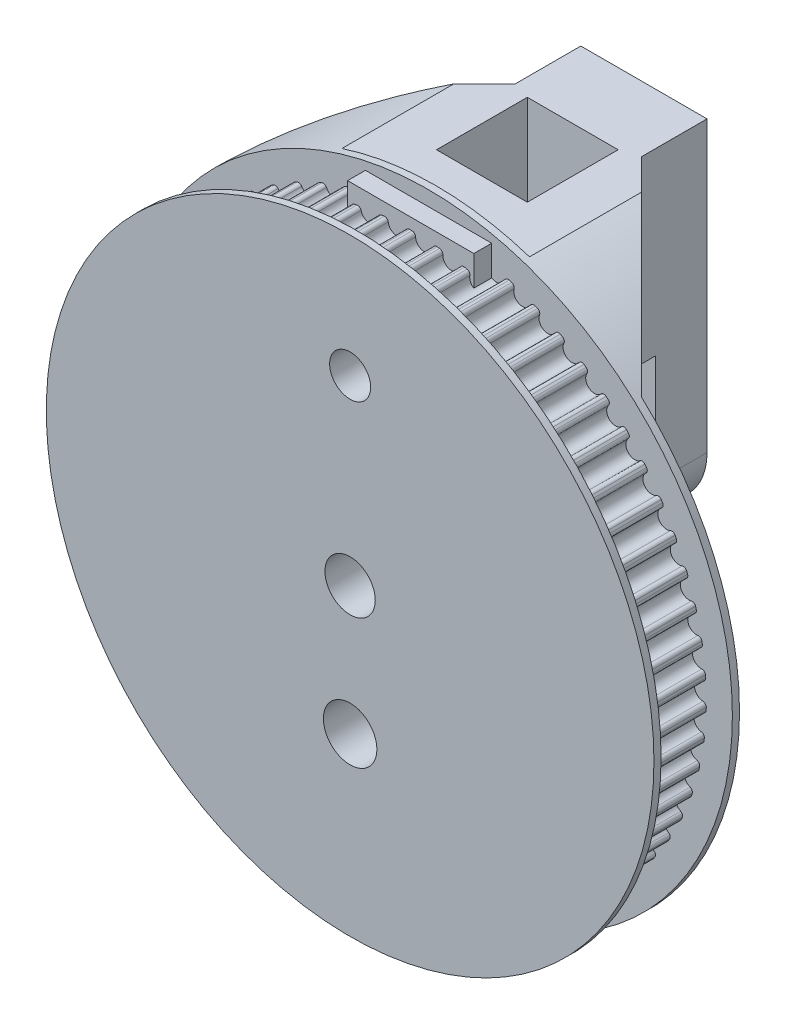
SolidWorks part; units mm, degrees
other "Markup1"
sketch "Sketch12" plane through (-30, -58, 49.7) normal (-0.8709, -0.4905, 0.0319) x (-0.1533, 0.2093, -0.9658)
other "Markup2"
sketch "Sketch14" plane through (30, -60, 49.7) normal (0.6168, -0.7172, 0.3243) x (-0.4689, -0.0038, 0.8832)
material "PETG"
ref_plane "Front Plane" through (0, 0, 0) normal (0, 0, 1) x (1, 0, 0)
ref_plane "Top Plane" through (0, 0, 0) normal (0, 1, 0) x (1, 0, 0)
ref_plane "Right Plane" through (0, 0, 0) normal (1, 0, 0) x (0, 0, -1)
sketch "Sketch1" plane through (0, 0, 0) normal (0, 1, 0) x (1, 0, 0)
  line L1 (-12.7375, -12.7375) -> (12.7375, -12.7375)
  line L2 (-12.7375, -12.7375) -> (-12.7375, 12.7375)
  line L3 (-12.7375, 12.7375) -> (12.7375, 12.7375)
  line L4 (12.7375, -12.7375) -> (12.7375, 12.7375)
  line L5 (-17.7, -17.7) -> (17.7, -17.7)
  line L6 (-17.7, -17.7) -> (-17.7, 17.7)
  line L7 (-17.7, 17.7) -> (17.7, 17.7)
  line L8 (17.7, -17.7) -> (17.7, 17.7)
  point P8 (0, -17.7)
  point P9 (0, -12.7375)
  point P12 (-17.7, 0)
  point P13 (-12.7375, 0)
  dimension "D1" = 25.475
  dimension "D2" = 35.4
extrude "Boss-Extrude1" add sketch "Sketch1" along normal blind 47.0375
extrude "Boss-Extrude2" add sketch "Sketch1<3>" against normal blind 14.9625 contours L1 L4 L3 L2 | L5 L8 L7 L6 L4 L1 L2 L3 region at (0, 0, 0) region at (-17.1994, 0, 0)
sketch "Sketch1<3>" plane through (0, 0, 0) normal (0, 1, 0) x (1, 0, 0) same geometry as "Sketch1"
sketch "Sketch3" plane through (0, 0, 0) normal (0, -1, 0) x (-1, 0, 0)
  circle A0 centre (0, 0) radius 3.15
  dimension "D1" = 6.3
extrude "Cut-Extrude1" cut sketch "Sketch3" along normal through all
sketch "Sketch13" plane through (0, -14.9625, 0) normal (0, -1, 0) x (1, 0, 0)
  circle A0 centre (0, 0) radius 5.5
  dimension "D1" = 11
extrude "Cut-Extrude4" cut sketch "Sketch13" against normal offset from surface (6.9625 mm away) 8 up to face at (0, 0, -3.15)
sketch "Sketch4" plane through (0, 0, 17.7) normal (0, 0, 1) x (1, 0, 0)
  line L0 (17.7, 47.0375) -> (17.7, -14.9625) construction
  line L1 (-17.7, 47.0375) -> (-17.7, -14.9625) construction
  line L2 (17.7, -34.0125) -> (17.7, -14.9625)
  line L3 (-17.7, -34.0125) -> (-17.7, -14.9625)
  line L5 (17.7, 47.0375) -> (-17.7, 47.0375)
  line L6 (17.7, 47.0375) -> (17.7, -14.9625)
  line L8 (-17.7, 47.0375) -> (-17.7, -14.9625)
  line L9 (-17.7, -14.9625) -> (17.7, -14.9625) construction
  line L10 (-17.7, 47.0375) -> (17.7, 47.0375) construction
  arc A0 (-17.7, -34.0125) -> (17.7, -34.0125) centre (0, -34.0125) ccw
  circle A1 centre (0, -34.0125) radius 7.05
  dimension "D2" = 14.1
  dimension "D1" = 19.05
extrude "Boss-Extrude3" add sketch "Sketch4" along normal blind 15
sketch "Sketch6" plane through (0, 0, 17.7) normal (0, 0, -1) x (-1, 0, 0)
  line L0 (17.7, -34.0125) -> (17.7, -14.9625)
  line L1 (17.7, -14.9625) -> (-17.7, -14.9625)
  line L2 (-17.7, -14.9625) -> (-17.7, -34.0125)
  arc A0 (-17.7, -34.0125) -> (17.7, -34.0125) centre (0, -34.0125) ccw
  arc A4 (-17.7, -34.0125) -> (17.7, -34.0125) centre (0, -34.0125) ccw construction
extrude "Cut-Extrude2" cut sketch "Sketch6" against normal blind 0.5375
sketch "Sketch7" plane through (0, 0, 18.2375) normal (0, 0, -1) x (-1, 0, 0)
  circle A0 centre (0, -34.0125) radius 11.0375
  arc A1 (-17.7, -34.0125) -> (17.7, -34.0125) centre (0, -34.0125) ccw construction
  dimension "D1" = 22.075
extrude "Cut-Extrude3" cut sketch "Sketch7" against normal blind 7
mirror "Mirror1" about plane through (0, 0, 0) normal (0, 0, 1) of "Boss-Extrude3", "Cut-Extrude2", "Cut-Extrude1", "Cut-Extrude3"
sketch "Sketch18" plane through (0, 0, 0) normal (0, 0, 1) x (1, 0, 0)
  line L0 (0, -13.5166) -> (-17.7, -3.2975)
  line L1 (-17.7, -3.2975) -> (-35.45, -34.0414) construction
  line L2 (-35.45, -34.0414) -> (-8.875, -49.3845) construction
  line L3 (-17.7, 47.0375) -> (-17.7, -34.0125) construction
  line L4 (0, -35.0322) -> (0, -50035.0322) construction
  line L5 (-17.7, -3.2975) -> (-17.7, -14.9625)
  line L6 (17.7, -34.0125) -> (17.7, 47.0375) construction
  line L7 (17.7, -3.2975) -> (0, -13.5166)
  line L10 (17.7, -14.9625) -> (17.7, -3.2975)
  line L11 (-17.7, -14.9625) -> (17.7, -14.9625)
  line L12 (-5.5, -14.9625) -> (5.5, -14.9625) construction
  circle A0 centre (0, -34.0125) radius 17.75 construction
  arc A2 (-17.7, -34.0125) -> (17.7, -34.0125) centre (0, -34.0125) ccw construction
  dimension "D2" = 120
  dimension "D1" = 35.5
extrude "Cut-Extrude10" cut sketch "Sketch18" along normal up to surface and the other way up to surface up to face at (-11.0375, -34.0125, 18.2375) other way up to face at (-11.0375, -34.0125, -18.2375)
ref_plane "Plane1" through (0, 0, 27.7) normal (0, 0, 1) x (1, 0, 0)
sketch "Sketch9" plane through (0, 0, 27.7) normal (0, 0, 1) x (1, 0, 0)
  circle A0 centre (0, -34.0125) radius 85.2141
  circle A1 centre (0, -34.0125) radius 7.05 construction
  circle A2 centre (0, -34.0125) radius 7.05
  dimension "D1" = 170.4282
extrude "Boss-Extrude4" add sketch "Sketch9" against normal blind 2 contours A0 region at (-82.8039, -34.0125, 27.7)
sketch "Sketch10" plane through (0, 0, 27.7) normal (0, 0, -1) x (-1, 0, 0)
  line L0 (0, -41.0625) -> (0, -50041.0625) construction
  line L1 (0, -34.0125) -> (-3.9983, -114.1269) construction
  line L2 (0, -34.0125) -> (3.9983, -114.1269) construction
  circle A0 centre (0, -34.0125) radius 80.2141 construction
  circle A1 centre (0, -34.0125) radius 7.05
  circle A2 centre (0, -34.0125) radius 85.2141 construction
  circle A3 centre (0, -34.0125) radius 7.05 construction
  arc A4 (2.4815, -110.9206) -> (-2.4815, -110.9206) centre (0, -111.1266) ccw
  arc A5 (-3.5233, -111.8369) -> (-2.4815, -110.9206) centre (-3.478, -110.8379) ccw
  circle A6 centre (0, -34.0125) radius 77.9041 construction
  arc A7 (2.4815, -110.9206) -> (3.5233, -111.8369) centre (3.478, -110.8379) ccw
  arc A8 (3.5233, -111.8369) -> (3.8832, -111.8198) centre (0, -34.0125) ccw
  arc A9 (-3.8832, -111.8198) -> (-3.5233, -111.8369) centre (0, -34.0125) ccw
  arc A10 (-11.611, -111.0465) -> (-11.2546, -111.0993) centre (0, -34.0125) ccw
  arc A11 (-11.2546, -111.0993) -> (-10.1267, -110.2914) centre (-11.1101, -110.1098) ccw
  arc A12 (-5.1884, -110.7855) -> (-10.1267, -110.2914) centre (-7.6781, -110.7434) ccw
  arc A13 (-5.1884, -110.7855) -> (-4.243, -111.801) centre (-4.1886, -110.8024) ccw
  arc A14 (-4.243, -111.801) -> (-3.8832, -111.8198) centre (0, -34.0125) ccw
  arc A15 (-19.2234, -109.5076) -> (-18.874, -109.5957) centre (0, -34.0125) ccw
  arc A16 (-18.874, -109.5957) -> (-17.6713, -108.904) centre (-18.6317, -108.6255) ccw
  arc A17 (-12.8068, -109.8874) -> (-17.6713, -108.904) centre (-15.2799, -109.5976) ccw
  arc A18 (-12.8068, -109.8874) -> (-11.9672, -110.9919) centre (-11.8136, -110.0038) ccw
  arc A19 (-11.9672, -110.9919) -> (-11.611, -111.0465) centre (0, -34.0125) ccw
  arc A20 (-26.6448, -107.2184) -> (-26.3059, -107.3409) centre (0, -34.0125) ccw
  arc A21 (-26.3059, -107.3409) -> (-25.0403, -106.7724) centre (-25.9682, -106.3996) ccw
  arc A22 (-20.2978, -108.2352) -> (-25.0403, -106.7724) centre (-22.7298, -107.7006) ccw
  arc A23 (-20.2978, -108.2352) -> (-19.5724, -109.4179) centre (-19.3212, -108.4499) ccw
  arc A24 (-19.5724, -109.4179) -> (-19.2234, -109.5076) centre (0, -34.0125) ccw
  arc A25 (-33.8013, -104.2017) -> (-33.4763, -104.3573) centre (0, -34.0125) ccw
  arc A26 (-33.4763, -104.3573) -> (-32.1604, -103.9176) centre (-33.0466, -103.4543) ccw
  arc A27 (-27.5872, -105.8454) -> (-32.1604, -103.9176) centre (-29.9538, -105.0713) ccw
  arc A28 (-27.5872, -105.8454) -> (-26.9831, -107.0944) centre (-26.6367, -106.1563) ccw
  arc A29 (-26.9831, -107.0944) -> (-26.6448, -107.2184) centre (0, -34.0125) ccw
  arc A30 (-40.6219, -100.4874) -> (-40.314, -100.6745) centre (0, -34.0125) ccw
  arc A31 (-40.314, -100.6745) -> (-38.9609, -100.3681) centre (-39.7965, -99.8188) ccw
  arc A32 (-34.6023, -102.7416) -> (-38.9609, -100.3681) centre (-36.8801, -101.7358) ccw
  arc A33 (-34.6023, -102.7416) -> (-34.1256, -104.0446) centre (-33.6876, -103.1456) ccw
  arc A34 (-34.1256, -104.0446) -> (-33.8013, -104.2017) centre (0, -34.0125) ccw
  arc A35 (-47.0388, -96.1124) -> (-46.7511, -96.3293) centre (0, -34.0125) ccw
  arc A36 (-46.7511, -96.3293) -> (-45.3742, -96.1591) centre (-46.151, -95.5294) ccw
  arc A37 (-41.2736, -98.9548) -> (-45.3742, -96.1591) centre (-43.4399, -97.7272) ccw
  arc A38 (-41.2736, -98.9548) -> (-40.929, -100.2987) centre (-40.4036, -99.4479) ccw
  arc A39 (-40.929, -100.2987) -> (-40.6219, -100.4874) centre (0, -34.0125) ccw
  arc A40 (-52.9882, -91.1202) -> (-52.7235, -91.3647) centre (0, -34.0125) ccw
  arc A41 (-52.7235, -91.3647) -> (-51.3365, -91.3325) centre (-52.0467, -90.6285) ccw
  arc A42 (-47.5347, -94.5226) -> (-51.3365, -91.3325) centre (-49.568, -93.0853) ccw
  arc A43 (-47.5347, -94.5226) -> (-47.3256, -95.8941) centre (-46.7181, -95.0998) ccw
  arc A44 (-47.3256, -95.8941) -> (-47.0388, -96.1124) centre (0, -34.0125) ccw
  arc A45 (-58.411, -85.5605) -> (-58.172, -85.8302) centre (0, -34.0125) ccw
  arc A46 (-58.172, -85.8302) -> (-56.7886, -85.9362) centre (-57.4253, -85.165) ccw
  arc A47 (-53.3233, -89.489) -> (-56.7886, -85.9362) centre (-55.2034, -87.8564) ccw
  arc A48 (-53.3233, -89.489) -> (-53.2518, -90.8745) centre (-52.5683, -90.1446) ccw
  arc A49 (-53.2518, -90.8745) -> (-52.9882, -91.1202) centre (0, -34.0125) ccw
  arc A50 (-63.2533, -79.4885) -> (-63.0423, -79.7806) centre (0, -34.0125) ccw
  arc A51 (-63.0423, -79.7806) -> (-61.6764, -80.0238) centre (-62.233, -79.1931) ccw
  arc A52 (-58.582, -83.904) -> (-61.6764, -80.0238) centre (-60.2902, -82.0923) ccw
  arc A53 (-58.582, -83.904) -> (-58.6488, -85.2898) centre (-57.896, -84.6316) ccw
  arc A54 (-58.6488, -85.2898) -> (-58.411, -85.5605) centre (0, -34.0125) ccw
  arc A55 (-67.4669, -72.9645) -> (-67.286, -73.2762) centre (0, -34.0125) ccw
  arc A56 (-67.286, -73.2762) -> (-65.9511, -73.6542) centre (-66.4223, -72.7722) ccw
  arc A57 (-63.2585, -77.8232) -> (-65.9511, -73.6542) centre (-64.7778, -75.8505) ccw
  arc A58 (-63.2585, -77.8232) -> (-63.463, -79.1955) centre (-62.6483, -78.6155) ccw
  arc A59 (-63.463, -79.1955) -> (-63.2533, -79.4885) centre (0, -34.0125) ccw
  arc A60 (-71.01, -66.0534) -> (-70.8611, -66.3816) centre (0, -34.0125) ccw
  arc A61 (-70.8611, -66.3816) -> (-69.5704, -66.8906) centre (-69.9515, -65.9661) ccw
  arc A62 (-67.3063, -71.307) -> (-69.5704, -66.8906) centre (-68.6217, -69.1928) ccw
  arc A63 (-67.3063, -71.307) -> (-67.6464, -72.6521) centre (-66.778, -72.1561) ccw
  arc A64 (-67.6464, -72.6521) -> (-67.4669, -72.9645) centre (0, -34.0125) ccw
  arc A65 (-73.8474, -58.8239) -> (-73.7319, -59.1652) centre (0, -34.0125) ccw
  arc A66 (-73.7319, -59.1652) -> (-72.4983, -59.8003) centre (-72.7854, -58.8424) ccw
  arc A67 (-70.6852, -64.4201) -> (-72.4983, -59.8003) centre (-71.7835, -62.1854) ccw
  arc A68 (-70.6852, -64.4201) -> (-71.1575, -65.7247) centre (-70.2441, -65.3176) ccw
  arc A69 (-71.1575, -65.7247) -> (-71.01, -66.0534) centre (0, -34.0125) ccw
  arc A70 (-75.9509, -51.3478) -> (-75.8699, -51.6989) centre (0, -34.0125) ccw
  arc A71 (-75.8699, -51.6989) -> (-74.7057, -52.4536) centre (-74.896, -51.4719) ccw
  arc A72 (-73.3615, -57.2311) -> (-74.7057, -52.4536) centre (-74.2319, -54.8981) ccw
  arc A73 (-73.3615, -57.2311) -> (-73.9614, -58.4821) centre (-73.012, -58.168) ccw
  arc A74 (-73.9614, -58.4821) -> (-73.8474, -58.8239) centre (0, -34.0125) ccw
  arc A75 (-77.2995, -43.6994) -> (-77.2539, -44.0568) centre (0, -34.0125) ccw
  arc A76 (-77.2539, -44.0568) -> (-76.1706, -44.9237) centre (-76.2622, -43.9279) ccw
  arc A77 (-75.3088, -49.8112) -> (-76.1706, -44.9237) centre (-75.9426, -47.4032) ccw
  arc A78 (-75.3088, -49.8112) -> (-76.0302, -50.9963) centre (-75.0543, -50.7783) ccw
  arc A79 (-76.0302, -50.9963) -> (-75.9509, -51.3478) centre (0, -34.0125) ccw
  arc A80 (-77.8799, -35.9547) -> (-77.8701, -36.3149) centre (0, -34.0125) ccw
  arc A81 (-77.8701, -36.3149) -> (-76.8785, -37.2853) centre (-76.8705, -36.2854) ccw
  arc A82 (-76.5076, -42.2344) -> (-76.8785, -37.2853) centre (-76.8985, -39.7752) ccw
  arc A83 (-76.5076, -42.2344) -> (-77.3435, -43.3417) centre (-76.3507, -43.222) ccw
  arc A84 (-77.3435, -43.3417) -> (-77.2995, -43.6994) centre (0, -34.0125) ccw
  arc A85 (-77.6863, -28.1907) -> (-77.7124, -28.5501) centre (0, -34.0125) ccw
  arc A86 (-77.7124, -28.5501) -> (-76.8224, -29.6144) centre (-76.7148, -28.6202) ccw
  arc A87 (-76.9461, -34.5758) -> (-76.8224, -29.6144) centre (-77.0901, -32.09) ccw
  arc A88 (-76.9461, -34.5758) -> (-77.888, -35.5945) centre (-76.8882, -35.5741) ccw
  arc A89 (-77.888, -35.5945) -> (-77.8799, -35.9547) centre (0, -34.0125) ccw
  arc A90 (-76.7206, -20.4846) -> (-76.7823, -20.8396) centre (0, -34.0125) ccw
  arc A91 (-76.7823, -20.8396) -> (-76.0027, -21.9873) centre (-75.7967, -21.0087) ccw
  arc A92 (-76.6198, -26.9117) -> (-76.0027, -21.9873) centre (-76.5156, -24.4238) ccw
  arc A93 (-76.6198, -26.9117) -> (-77.6585, -27.8315) centre (-76.6616, -27.9108) ccw
  arc A94 (-77.6585, -27.8315) -> (-77.6863, -28.1907) centre (0, -34.0125) ccw
  arc A95 (-74.9924, -12.9129) -> (-75.0892, -13.26) centre (0, -34.0125) ccw
  arc A96 (-75.0892, -13.26) -> (-74.4277, -14.4796) centre (-74.1253, -13.5264) ccw
  arc A97 (-75.5321, -19.3181) -> (-74.4277, -14.4796) centre (-75.1807, -16.853) ccw
  arc A98 (-75.5321, -19.3181) -> (-76.6572, -20.1299) centre (-75.6732, -20.3081) ccw
  arc A99 (-76.6572, -20.1299) -> (-76.7206, -20.4846) centre (0, -34.0125) ccw
  arc A100 (-72.5189, -5.5509) -> (-72.6497, -5.8867) centre (0, -34.0125) ccw
  arc A101 (-72.6497, -5.8867) -> (-72.113, -7.166) centre (-71.7172, -6.2477) ccw
  arc A102 (-73.6936, -11.8705) -> (-72.113, -7.166) centre (-73.0986, -9.4527) ccw
  arc A103 (-73.6936, -11.8705) -> (-74.894, -12.5663) centre (-73.9326, -12.8416) ccw
  arc A104 (-74.894, -12.5663) -> (-74.9924, -12.9129) centre (0, -34.0125) ccw
  arc A105 (-69.3247, 1.5282) -> (-69.4883, 1.2071) centre (0, -34.0125) ccw
  arc A106 (-69.4883, 1.2071) -> (-69.0816, -0.1193) centre (-68.5963, 0.7551) ccw
  arc A107 (-71.1228, -4.6431) -> (-69.0816, -0.1193) centre (-70.2899, -2.2965) ccw
  arc A108 (-71.1228, -4.6431) -> (-72.3865, -5.2158) centre (-71.4573, -5.5855) ccw
  arc A109 (-72.3865, -5.2158) -> (-72.5189, -5.5509) centre (0, -34.0125) ccw
  arc A110 (-65.4415, 8.2541) -> (-65.6363, 7.9509) centre (0, -34.0125) ccw
  arc A111 (-65.6363, 7.9509) -> (-65.3637, 6.5906) centre (-64.7937, 7.4123) ccw
  arc A112 (-67.8451, 2.2925) -> (-65.3637, 6.5906) centre (-66.7828, 4.5445) ccw
  arc A113 (-67.8451, 2.2925) -> (-69.1595, 1.8485) centre (-68.2718, 1.3881) ccw
  arc A114 (-69.1595, 1.8485) -> (-69.3247, 1.5282) centre (0, -34.0125) ccw
  arc A115 (-60.9079, 14.5599) -> (-61.1319, 14.2777) centre (0, -34.0125) ccw
  arc A116 (-61.1319, 14.2777) -> (-60.9961, 12.8969) centre (-60.3472, 13.6578) ccw
  arc A117 (-63.8932, 8.8673) -> (-60.9961, 12.8969) centre (-62.6119, 11.0024) ccw
  arc A118 (-63.8932, 8.8673) -> (-65.2453, 8.5563) centre (-64.4077, 8.0099) ccw
  arc A119 (-65.2453, 8.5563) -> (-65.4415, 8.2541) centre (0, -34.0125) ccw
  arc A120 (-55.769, 20.383) -> (-56.02, 20.1245) centre (0, -34.0125) ccw
  arc A121 (-56.02, 20.1245) -> (-56.0223, 18.7371) centre (-55.3009, 19.4295) ccw
  arc A122 (-59.3062, 15.016) -> (-56.0223, 18.7371) centre (-57.8187, 17.0128) ccw
  arc A123 (-59.3062, 15.016) -> (-60.6826, 14.8411) centre (-59.9036, 14.214) ccw
  arc A124 (-60.6826, 14.8411) -> (-60.9079, 14.5599) centre (0, -34.0125) ccw
  arc A125 (-50.0758, 25.6655) -> (-50.3513, 25.4332) centre (0, -34.0125) ccw
  arc A126 (-50.3513, 25.4332) -> (-50.4918, 24.053) centre (-49.705, 24.6702) ccw
  arc A127 (-54.1299, 20.6773) -> (-50.4918, 24.053) centre (-52.4509, 22.5161) ccw
  arc A128 (-54.1299, 20.6773) -> (-55.5168, 20.6404) centre (-54.8041, 19.9388) ccw
  arc A129 (-55.5168, 20.6404) -> (-55.769, 20.383) centre (0, -34.0125) ccw
  arc A130 (-43.8849, 30.3549) -> (-44.1822, 30.1512) centre (0, -34.0125) ccw
  arc A131 (-44.1822, 30.1512) -> (-44.4594, 28.7918) centre (-43.6151, 29.3276) ccw
  arc A132 (-48.4155, 25.7951) -> (-44.4594, 28.7918) centre (-46.5618, 27.4576) ccw
  arc A133 (-48.4155, 25.7951) -> (-49.7992, 25.8965) centre (-49.16, 25.1275) ccw
  arc A134 (-49.7992, 25.8965) -> (-50.0758, 25.6655) centre (0, -34.0125) ccw
  arc A135 (-37.2579, 34.4046) -> (-37.574, 34.2315) centre (0, -34.0125) ccw
  arc A136 (-37.574, 34.2315) -> (-37.9852, 32.9064) centre (-37.0917, 33.3555) ccw
  arc A137 (-42.22, 30.3186) -> (-37.9852, 32.9064) centre (-40.21, 31.7883) ccw
  arc A138 (-42.22, 30.3186) -> (-43.5867, 30.5572) centre (-43.0272, 29.7283) ccw
  arc A139 (-43.5867, 30.5572) -> (-43.8849, 30.3549) centre (0, -34.0125) ccw
  arc A140 (-30.2607, 37.7743) -> (-30.5924, 37.6335) centre (0, -34.0125) ccw
  arc A141 (-30.5924, 37.6335) -> (-31.1335, 36.356) centre (-30.1997, 36.7139) ccw
  arc A142 (-35.6049, 34.2027) -> (-31.1335, 36.356) centre (-33.4586, 35.4649) ccw
  arc A143 (-35.6049, 34.2027) -> (-36.9411, 34.5762) centre (-36.4669, 33.6957) ccw
  arc A144 (-36.9411, 34.5762) -> (-37.2579, 34.4046) centre (0, -34.0125) ccw
  arc A145 (-22.9626, 40.4305) -> (-23.3067, 40.3235) centre (0, -34.0125) ccw
  arc A146 (-23.3067, 40.3235) -> (-23.9723, 39.1062) centre (-23.0075, 39.3693) ccw
  arc A147 (-28.6359, 37.4088) -> (-23.9723, 39.1062) centre (-26.3746, 38.451) ccw
  arc A148 (-28.6359, 37.4088) -> (-29.9283, 37.9135) centre (-29.5441, 36.9902) ccw
  arc A149 (-29.9283, 37.9135) -> (-30.2607, 37.7743) centre (0, -34.0125) ccw
  arc A150 (-15.4364, 42.3469) -> (-15.7894, 42.2747) centre (0, -34.0125) ccw
  arc A151 (-15.7894, 42.2747) -> (-16.5729, 41.1297) centre (-15.5867, 41.2955) ccw
  arc A152 (-21.3824, 39.9051) -> (-16.5729, 41.1297) centre (-19.0285, 40.717) ccw
  arc A153 (-21.3824, 39.9051) -> (-22.6181, 40.5359) centre (-22.3277, 39.579) ccw
  arc A154 (-22.6181, 40.5359) -> (-22.9626, 40.4305) centre (0, -34.0125) ccw
  arc A155 (-7.7567, 43.5045) -> (-8.1152, 43.4678) centre (0, -34.0125) ccw
  arc A156 (-8.1152, 43.4678) -> (-9.0088, 42.4065) centre (-8.011, 42.4732) ccw
  arc A157 (-13.9163, 41.6668) -> (-9.0088, 42.4065) centre (-11.4933, 42.2403) ccw
  arc A158 (-13.9163, 41.6668) -> (-15.083, 42.4175) centre (-14.8894, 41.4365) ccw
  arc A159 (-15.083, 42.4175) -> (-15.4364, 42.3469) centre (0, -34.0125) ccw
  arc A160 (0, 43.8916) -> (-0.3603, 43.8908) centre (0, -34.0125) ccw
  arc A161 (-0.3603, 43.8908) -> (-1.3552, 42.9237) centre (-0.3557, 42.8908) ccw
  arc A162 (-6.3119, 42.6763) -> (-1.3552, 42.9237) centre (-3.8438, 43.0057) ccw
  arc A163 (-6.3119, 42.6763) -> (-7.3981, 43.5395) centre (-7.3031, 42.544) ccw
  arc A164 (-7.3981, 43.5395) -> (-7.7567, 43.5045) centre (0, -34.0125) ccw
  arc A165 (7.7567, 43.5045) -> (7.3981, 43.5395) centre (0, -34.0125) ccw
  arc A166 (7.3981, 43.5395) -> (6.3119, 42.6763) centre (7.3031, 42.544) ccw
  arc A167 (1.3552, 42.9237) -> (6.3119, 42.6763) centre (3.8438, 43.0057) ccw
  arc A168 (1.3552, 42.9237) -> (0.3603, 43.8908) centre (0.3557, 42.8908) ccw
  arc A169 (0.3603, 43.8908) -> (0, 43.8916) centre (0, -34.0125) ccw
  arc A170 (15.4364, 42.3469) -> (15.083, 42.4175) centre (0, -34.0125) ccw
  arc A171 (15.083, 42.4175) -> (13.9163, 41.6668) centre (14.8894, 41.4365) ccw
  arc A172 (9.0088, 42.4065) -> (13.9163, 41.6668) centre (11.4933, 42.2403) ccw
  arc A173 (9.0088, 42.4065) -> (8.1152, 43.4678) centre (8.011, 42.4732) ccw
  arc A174 (8.1152, 43.4678) -> (7.7567, 43.5045) centre (0, -34.0125) ccw
  arc A175 (22.9626, 40.4305) -> (22.6181, 40.5359) centre (0, -34.0125) ccw
  arc A176 (22.6181, 40.5359) -> (21.3824, 39.9051) centre (22.3277, 39.579) ccw
  arc A177 (16.5729, 41.1297) -> (21.3824, 39.9051) centre (19.0285, 40.717) ccw
  arc A178 (16.5729, 41.1297) -> (15.7894, 42.2747) centre (15.5867, 41.2955) ccw
  arc A179 (15.7894, 42.2747) -> (15.4364, 42.3469) centre (0, -34.0125) ccw
  arc A180 (30.2607, 37.7743) -> (29.9283, 37.9135) centre (0, -34.0125) ccw
  arc A181 (29.9283, 37.9135) -> (28.6359, 37.4088) centre (29.5441, 36.9902) ccw
  arc A182 (23.9723, 39.1062) -> (28.6359, 37.4088) centre (26.3746, 38.451) ccw
  arc A183 (23.9723, 39.1062) -> (23.3067, 40.3235) centre (23.0075, 39.3693) ccw
  arc A184 (23.3067, 40.3235) -> (22.9626, 40.4305) centre (0, -34.0125) ccw
  arc A185 (37.2579, 34.4046) -> (36.9411, 34.5762) centre (0, -34.0125) ccw
  arc A186 (36.9411, 34.5762) -> (35.6049, 34.2027) centre (36.4669, 33.6957) ccw
  arc A187 (31.1335, 36.356) -> (35.6049, 34.2027) centre (33.4586, 35.4649) ccw
  arc A188 (31.1335, 36.356) -> (30.5924, 37.6335) centre (30.1997, 36.7139) ccw
  arc A189 (30.5924, 37.6335) -> (30.2607, 37.7743) centre (0, -34.0125) ccw
  arc A190 (43.8849, 30.3549) -> (43.5867, 30.5572) centre (0, -34.0125) ccw
  arc A191 (43.5867, 30.5572) -> (42.22, 30.3186) centre (43.0272, 29.7283) ccw
  arc A192 (37.9852, 32.9064) -> (42.22, 30.3186) centre (40.21, 31.7883) ccw
  arc A193 (37.9852, 32.9064) -> (37.574, 34.2315) centre (37.0917, 33.3555) ccw
  arc A194 (37.574, 34.2315) -> (37.2579, 34.4046) centre (0, -34.0125) ccw
  arc A195 (50.0758, 25.6655) -> (49.7992, 25.8965) centre (0, -34.0125) ccw
  arc A196 (49.7992, 25.8965) -> (48.4155, 25.7951) centre (49.16, 25.1275) ccw
  arc A197 (44.4594, 28.7918) -> (48.4155, 25.7951) centre (46.5618, 27.4576) ccw
  arc A198 (44.4594, 28.7918) -> (44.1822, 30.1512) centre (43.6151, 29.3276) ccw
  arc A199 (44.1822, 30.1512) -> (43.8849, 30.3549) centre (0, -34.0125) ccw
  arc A200 (55.769, 20.383) -> (55.5168, 20.6404) centre (0, -34.0125) ccw
  arc A201 (55.5168, 20.6404) -> (54.1299, 20.6773) centre (54.8041, 19.9388) ccw
  arc A202 (50.4918, 24.053) -> (54.1299, 20.6773) centre (52.4509, 22.5161) ccw
  arc A203 (50.4918, 24.053) -> (50.3513, 25.4332) centre (49.705, 24.6702) ccw
  arc A204 (50.3513, 25.4332) -> (50.0758, 25.6655) centre (0, -34.0125) ccw
  arc A205 (60.9079, 14.5599) -> (60.6826, 14.8411) centre (0, -34.0125) ccw
  arc A206 (60.6826, 14.8411) -> (59.3062, 15.016) centre (59.9036, 14.214) ccw
  arc A207 (56.0223, 18.7371) -> (59.3062, 15.016) centre (57.8187, 17.0128) ccw
  arc A208 (56.0223, 18.7371) -> (56.02, 20.1245) centre (55.3009, 19.4295) ccw
  arc A209 (56.02, 20.1245) -> (55.769, 20.383) centre (0, -34.0125) ccw
  arc A210 (65.4415, 8.2541) -> (65.2453, 8.5563) centre (0, -34.0125) ccw
  arc A211 (65.2453, 8.5563) -> (63.8932, 8.8673) centre (64.4077, 8.0099) ccw
  arc A212 (60.9961, 12.8969) -> (63.8932, 8.8673) centre (62.6119, 11.0024) ccw
  arc A213 (60.9961, 12.8969) -> (61.1319, 14.2777) centre (60.3472, 13.6578) ccw
  arc A214 (61.1319, 14.2777) -> (60.9079, 14.5599) centre (0, -34.0125) ccw
  arc A215 (69.3247, 1.5282) -> (69.1595, 1.8485) centre (0, -34.0125) ccw
  arc A216 (69.1595, 1.8485) -> (67.8451, 2.2925) centre (68.2718, 1.3881) ccw
  arc A217 (65.3637, 6.5906) -> (67.8451, 2.2925) centre (66.7828, 4.5445) ccw
  arc A218 (65.3637, 6.5906) -> (65.6363, 7.9509) centre (64.7937, 7.4123) ccw
  arc A219 (65.6363, 7.9509) -> (65.4415, 8.2541) centre (0, -34.0125) ccw
  arc A220 (72.5189, -5.5509) -> (72.3865, -5.2158) centre (0, -34.0125) ccw
  arc A221 (72.3865, -5.2158) -> (71.1228, -4.6431) centre (71.4573, -5.5855) ccw
  arc A222 (69.0816, -0.1193) -> (71.1228, -4.6431) centre (70.2899, -2.2965) ccw
  arc A223 (69.0816, -0.1193) -> (69.4883, 1.2071) centre (68.5963, 0.7551) ccw
  arc A224 (69.4883, 1.2071) -> (69.3247, 1.5282) centre (0, -34.0125) ccw
  arc A225 (74.9924, -12.9129) -> (74.894, -12.5663) centre (0, -34.0125) ccw
  arc A226 (74.894, -12.5663) -> (73.6936, -11.8705) centre (73.9326, -12.8416) ccw
  arc A227 (72.113, -7.166) -> (73.6936, -11.8705) centre (73.0986, -9.4527) ccw
  arc A228 (72.113, -7.166) -> (72.6497, -5.8867) centre (71.7172, -6.2477) ccw
  arc A229 (72.6497, -5.8867) -> (72.5189, -5.5509) centre (0, -34.0125) ccw
  arc A230 (76.7206, -20.4846) -> (76.6572, -20.1299) centre (0, -34.0125) ccw
  arc A231 (76.6572, -20.1299) -> (75.5321, -19.3181) centre (75.6732, -20.3081) ccw
  arc A232 (74.4277, -14.4796) -> (75.5321, -19.3181) centre (75.1807, -16.853) ccw
  arc A233 (74.4277, -14.4796) -> (75.0892, -13.26) centre (74.1253, -13.5264) ccw
  arc A234 (75.0892, -13.26) -> (74.9924, -12.9129) centre (0, -34.0125) ccw
  arc A235 (77.6863, -28.1907) -> (77.6585, -27.8315) centre (0, -34.0125) ccw
  arc A236 (77.6585, -27.8315) -> (76.6198, -26.9117) centre (76.6616, -27.9108) ccw
  arc A237 (76.0027, -21.9873) -> (76.6198, -26.9117) centre (76.5156, -24.4238) ccw
  arc A238 (76.0027, -21.9873) -> (76.7823, -20.8396) centre (75.7967, -21.0087) ccw
  arc A239 (76.7823, -20.8396) -> (76.7206, -20.4846) centre (0, -34.0125) ccw
  arc A240 (77.8799, -35.9547) -> (77.888, -35.5945) centre (0, -34.0125) ccw
  arc A241 (77.888, -35.5945) -> (76.9461, -34.5758) centre (76.8882, -35.5741) ccw
  arc A242 (76.8224, -29.6144) -> (76.9461, -34.5758) centre (77.0901, -32.09) ccw
  arc A243 (76.8224, -29.6144) -> (77.7124, -28.5501) centre (76.7148, -28.6202) ccw
  arc A244 (77.7124, -28.5501) -> (77.6863, -28.1907) centre (0, -34.0125) ccw
  arc A245 (77.2995, -43.6994) -> (77.3435, -43.3417) centre (0, -34.0125) ccw
  arc A246 (77.3435, -43.3417) -> (76.5076, -42.2344) centre (76.3507, -43.222) ccw
  arc A247 (76.8785, -37.2853) -> (76.5076, -42.2344) centre (76.8985, -39.7752) ccw
  arc A248 (76.8785, -37.2853) -> (77.8701, -36.3149) centre (76.8705, -36.2854) ccw
  arc A249 (77.8701, -36.3149) -> (77.8799, -35.9547) centre (0, -34.0125) ccw
  arc A250 (75.9509, -51.3478) -> (76.0302, -50.9963) centre (0, -34.0125) ccw
  arc A251 (76.0302, -50.9963) -> (75.3088, -49.8112) centre (75.0543, -50.7783) ccw
  arc A252 (76.1706, -44.9237) -> (75.3088, -49.8112) centre (75.9426, -47.4032) ccw
  arc A253 (76.1706, -44.9237) -> (77.2539, -44.0568) centre (76.2622, -43.9279) ccw
  arc A254 (77.2539, -44.0568) -> (77.2995, -43.6994) centre (0, -34.0125) ccw
  arc A255 (73.8474, -58.8239) -> (73.9614, -58.4821) centre (0, -34.0125) ccw
  arc A256 (73.9614, -58.4821) -> (73.3615, -57.2311) centre (73.012, -58.168) ccw
  arc A257 (74.7057, -52.4536) -> (73.3615, -57.2311) centre (74.2319, -54.8981) ccw
  arc A258 (74.7057, -52.4536) -> (75.8699, -51.6989) centre (74.896, -51.4719) ccw
  arc A259 (75.8699, -51.6989) -> (75.9509, -51.3478) centre (0, -34.0125) ccw
  arc A260 (71.01, -66.0534) -> (71.1575, -65.7247) centre (0, -34.0125) ccw
  arc A261 (71.1575, -65.7247) -> (70.6852, -64.4201) centre (70.2441, -65.3176) ccw
  arc A262 (72.4983, -59.8003) -> (70.6852, -64.4201) centre (71.7835, -62.1854) ccw
  arc A263 (72.4983, -59.8003) -> (73.7319, -59.1652) centre (72.7854, -58.8424) ccw
  arc A264 (73.7319, -59.1652) -> (73.8474, -58.8239) centre (0, -34.0125) ccw
  arc A265 (67.4669, -72.9645) -> (67.6464, -72.6521) centre (0, -34.0125) ccw
  arc A266 (67.6464, -72.6521) -> (67.3063, -71.307) centre (66.778, -72.1561) ccw
  arc A267 (69.5704, -66.8906) -> (67.3063, -71.307) centre (68.6217, -69.1928) ccw
  arc A268 (69.5704, -66.8906) -> (70.8611, -66.3816) centre (69.9515, -65.9661) ccw
  arc A269 (70.8611, -66.3816) -> (71.01, -66.0534) centre (0, -34.0125) ccw
  arc A270 (63.2533, -79.4885) -> (63.463, -79.1955) centre (0, -34.0125) ccw
  arc A271 (63.463, -79.1955) -> (63.2585, -77.8232) centre (62.6483, -78.6155) ccw
  arc A272 (65.9511, -73.6542) -> (63.2585, -77.8232) centre (64.7778, -75.8505) ccw
  arc A273 (65.9511, -73.6542) -> (67.286, -73.2762) centre (66.4223, -72.7722) ccw
  arc A274 (67.286, -73.2762) -> (67.4669, -72.9645) centre (0, -34.0125) ccw
  arc A275 (58.411, -85.5605) -> (58.6488, -85.2898) centre (0, -34.0125) ccw
  arc A276 (58.6488, -85.2898) -> (58.582, -83.904) centre (57.896, -84.6316) ccw
  arc A277 (61.6764, -80.0238) -> (58.582, -83.904) centre (60.2902, -82.0923) ccw
  arc A278 (61.6764, -80.0238) -> (63.0423, -79.7806) centre (62.233, -79.1931) ccw
  arc A279 (63.0423, -79.7806) -> (63.2533, -79.4885) centre (0, -34.0125) ccw
  arc A280 (52.9882, -91.1202) -> (53.2518, -90.8745) centre (0, -34.0125) ccw
  arc A281 (53.2518, -90.8745) -> (53.3233, -89.489) centre (52.5683, -90.1446) ccw
  arc A282 (56.7886, -85.9362) -> (53.3233, -89.489) centre (55.2034, -87.8564) ccw
  arc A283 (56.7886, -85.9362) -> (58.172, -85.8302) centre (57.4253, -85.165) ccw
  arc A284 (58.172, -85.8302) -> (58.411, -85.5605) centre (0, -34.0125) ccw
  arc A285 (47.0388, -96.1124) -> (47.3256, -95.8941) centre (0, -34.0125) ccw
  arc A286 (47.3256, -95.8941) -> (47.5347, -94.5226) centre (46.7181, -95.0998) ccw
  arc A287 (51.3365, -91.3325) -> (47.5347, -94.5226) centre (49.568, -93.0853) ccw
  arc A288 (51.3365, -91.3325) -> (52.7235, -91.3647) centre (52.0467, -90.6285) ccw
  arc A289 (52.7235, -91.3647) -> (52.9882, -91.1202) centre (0, -34.0125) ccw
  arc A290 (40.6219, -100.4874) -> (40.929, -100.2987) centre (0, -34.0125) ccw
  arc A291 (40.929, -100.2987) -> (41.2736, -98.9548) centre (40.4036, -99.4479) ccw
  arc A292 (45.3742, -96.1591) -> (41.2736, -98.9548) centre (43.4399, -97.7272) ccw
  arc A293 (45.3742, -96.1591) -> (46.7511, -96.3293) centre (46.151, -95.5294) ccw
  arc A294 (46.7511, -96.3293) -> (47.0388, -96.1124) centre (0, -34.0125) ccw
  arc A295 (33.8013, -104.2017) -> (34.1256, -104.0446) centre (0, -34.0125) ccw
  arc A296 (34.1256, -104.0446) -> (34.6023, -102.7416) centre (33.6876, -103.1456) ccw
  arc A297 (38.9609, -100.3681) -> (34.6023, -102.7416) centre (36.8801, -101.7358) ccw
  arc A298 (38.9609, -100.3681) -> (40.314, -100.6745) centre (39.7965, -99.8188) ccw
  arc A299 (40.314, -100.6745) -> (40.6219, -100.4874) centre (0, -34.0125) ccw
  arc A300 (26.6448, -107.2184) -> (26.9831, -107.0944) centre (0, -34.0125) ccw
  arc A301 (26.9831, -107.0944) -> (27.5872, -105.8454) centre (26.6367, -106.1563) ccw
  arc A302 (32.1604, -103.9176) -> (27.5872, -105.8454) centre (29.9538, -105.0713) ccw
  arc A303 (32.1604, -103.9176) -> (33.4763, -104.3573) centre (33.0466, -103.4543) ccw
  arc A304 (33.4763, -104.3573) -> (33.8013, -104.2017) centre (0, -34.0125) ccw
  arc A305 (19.2234, -109.5076) -> (19.5724, -109.4179) centre (0, -34.0125) ccw
  arc A306 (19.5724, -109.4179) -> (20.2978, -108.2352) centre (19.3212, -108.4499) ccw
  arc A307 (25.0403, -106.7724) -> (20.2978, -108.2352) centre (22.7298, -107.7006) ccw
  arc A308 (25.0403, -106.7724) -> (26.3059, -107.3409) centre (25.9682, -106.3996) ccw
  arc A309 (26.3059, -107.3409) -> (26.6448, -107.2184) centre (0, -34.0125) ccw
  arc A310 (11.611, -111.0465) -> (11.9672, -110.9919) centre (0, -34.0125) ccw
  arc A311 (11.9672, -110.9919) -> (12.8068, -109.8874) centre (11.8136, -110.0038) ccw
  arc A312 (17.6713, -108.904) -> (12.8068, -109.8874) centre (15.2799, -109.5976) ccw
  arc A313 (17.6713, -108.904) -> (18.874, -109.5957) centre (18.6317, -108.6255) ccw
  arc A314 (18.874, -109.5957) -> (19.2234, -109.5076) centre (0, -34.0125) ccw
  arc A315 (3.8832, -111.8198) -> (4.243, -111.801) centre (0, -34.0125) ccw
  arc A316 (4.243, -111.801) -> (5.1884, -110.7855) centre (4.1886, -110.8024) ccw
  arc A317 (10.1267, -110.2914) -> (5.1884, -110.7855) centre (7.6781, -110.7434) ccw
  arc A318 (10.1267, -110.2914) -> (11.2546, -111.0993) centre (11.1101, -110.1098) ccw
  arc A319 (11.2546, -111.0993) -> (11.611, -111.0465) centre (0, -34.0125) ccw
  point P10 (0, -108.6366)
  point P14 (0, -111.9166)
  point P27 (0, -114.2266)
  arc M13 (-17.7, -34.0125) -> (17.7, -34.0125) centre (0, -34.0125) ccw
  line M14 (17.7, -34.0125) -> (17.7, 47.0375)
  line M16 (-17.7, 47.0375) -> (-17.7, -34.0125)
  dimension "D1" = 160.4282
  dimension "D2" = 2.49
  dimension "D3" = 1
  dimension "D4" = 3.28
  dimension "D6" = 5.59
  dimension "D5" = 8
  dimension "D7" = 63
extrude "Boss-Extrude5" add sketch "Sketch10" against normal blind 20 contours A8 A7 A4 A5 A9 A14 A13 A12 A11 A10 A19 A18 A17 A16 A15 A24 A23 A22 A21 A20 A29 A28 A27 A26 A25 A34 A33 A32 A31 A30 A39 A38 A37 A36 A35 A44 A43 A42 A41 A40 A49 A48 A47 A46 A45 A54 | A179 A178 A177 A152 A151 A150 A159 A158 A157 A156 A155 A164 A163 A162 A161 A160 A169 A168 A167 A166 A165 A174 A173 A172 A171 A170 A1 M14 M13 M16 region at (0, -106.4572, 27.7) region at (0, -1.7178, 27.7)
sketch "Sketch11" plane through (0, 0, 47.7) normal (0, 0, 1) x (1, 0, 0)
  circle A0 centre (0, -34.0125) radius 85.2141
  circle A1 centre (0, -34.0125) radius 7.05
  circle A3 centre (0, -34.0125) radius 85.2141 construction
  circle A4 centre (0, -34.0125) radius 7.05 construction
extrude "Boss-Extrude6" add sketch "Sketch11" along normal blind 2 contours A0 region at (-82.8039, -34.0125, 47.7)
sketch "Sketch15" plane through (0, 0, -32.7) normal (0, 0, -1) x (-1, 0, 0)
  line L1 (0, 17.0375) -> (-17.7, 17.0375) construction
  line L2 (0, 17.0375) -> (17.7, 17.0375) construction
  line L3 (17.7, 47.0375) -> (17.7, -34.0125) construction
  line L4 (-17.7, -34.0125) -> (-17.7, 47.0375) construction
  line L5 (-17.7, 47.0375) -> (17.7, 47.0375) construction
  circle A0 centre (0, 17.0375) radius 3.25
  dimension "D1" = 6.5
  dimension "D2" = 30
extrude "Cut-Extrude5" cut sketch "Sketch15" against normal up to next
sketch "Sketch16" plane through (0, 0, -32.7) normal (0, 0, -1) x (-1, 0, 0)
  circle A0 centre (0, 17.0375) radius 5.75
  circle A1 centre (0, 17.0375) radius 3.25 construction
  dimension "D1" = 11.5
extrude "Cut-Extrude6" cut sketch "Sketch16" against normal blind 10 and the other way through all
mirror "Mirror2" about plane through (0, 0, 0) normal (0, 0, 1) of "Cut-Extrude5", "Cut-Extrude6"
sketch "Sketch17" plane through (0, 0, 25.7) normal (0, 0, -1) x (-1, 0, 0)
  line L0 (8.875, -49.3845) -> (81.0538, -7.712) construction
  line L1 (81.0538, -7.712) -> (63.3038, 23.0319) construction
  line L2 (63.3038, 23.0319) -> (-8.875, -18.6405) construction
  line L3 (0, -31.0125) -> (0, -50031.0125) construction
  line L4 (17.7, -3.2975) -> (17.7, 47.0375)
  line L5 (17.7, 47.0375) -> (17.7, -34.0125) construction
  line L6 (17.7, 47.0375) -> (17.7, -34.0125) construction
  line L8 (57.7, 28.6944) -> (57.7, 19.7965)
  line L9 (57.7, 19.7965) -> (17.7, -3.2975)
  line L10 (17.7, 47.0375) -> (26.3123, 47.0375)
  circle A0 centre (0, -34.0125) radius 17.75 construction
  circle A1 centre (0, -34.0125) radius 85.2141 construction
  arc A3 (57.7, 28.6944) -> (26.3123, 47.0375) centre (0, -34.0125) ccw
  dimension "D2" = 120
  dimension "D3" = 40
  dimension "D1" = 35.5
extrude "Boss-Extrude7" add sketch "Sketch17" along normal blind 40
chamfer "Chamfer1" distance 40 angle 45 1 edges at (-57.7, 24.2455, -14.3)
mirror "Mirror3" about plane through (0, 0, 0) normal (1, 0, 0) of "Chamfer1", "Boss-Extrude7"
sketch "Sketch19" plane through (0, 0, 49.7) normal (0, 0, 1) x (1, 0, 0)
  circle A0 centre (0, -70.0125) radius 7.5
  circle A1 centre (0, -34.0125) radius 7.05 construction
  point P4 (0, 0)
  dimension "D1" = 36
  dimension "D2" = 15
extrude "Cut-Extrude11" cut sketch "Sketch19" against normal through all
equation "\"tol_dia_id_intfc\" = 0.0500mm ' For hole diameters - Interference fit"
equation "\"tol_dia_id_slip\"  = 0.0750mm ' For hole diameters - Slip fit"
equation "\"tol_dia_id_clear\" = 0.1000mm ' For hole diameters - Clearance fit"
equation "\"tol_dia_od_intfc\" = 0.0500mm ' For shaft diameters - Interference fit"
equation "\"tol_dia_od_slip\"  = 0.0750mm ' For shaft diameters - Slip fit"
equation "\"tol_dia_od_clear\" = 0.1000mm ' For shaft diameters - Clearance fit"
equation "\"tol_general_intfc\"= 0.0250mm ' For general parts (Horiz) - Interference fit"
equation "\"tol_general_slip\" = 0.0375mm ' For general parts (Horiz) - Slip fit"
equation "\"tol_general_clear\"= 0.0500mm ' For general parts (Horiz) - Clearance fit"
equation "\"tol_layer_intfc\"  = 0.0250mm ' For all parts (Vert) - Interference fit"
equation "\"tol_layer_slip\"   = 0.0375mm ' For all parts (Vert) - Slip fit"
equation "\"tol_layer_clear\"  = 0.0500mm ' For all parts (Vert) - Clearance fit"
equation "\"tol_corner_rad\"   = 0.100mm ' For corners that fit into other parts"
equation "\"pitch\"= 8mm"
equation "\"n\"=63"
equation "\"pitch_dia\"= \"pitch\" * \"n\" / PI"
equation "\"belt_width\"= 20mm"
equation "\"pulley_chamfer\"= 40mm"
equation "\"D1@Sketch1\"= 25.4 + \"tol_general_slip\" * 2"
equation "\"D2@Sketch1\"=25.4+10"
equation "\"D1@Boss-Extrude1\"=47.00mm+\"tol_layer_slip\""
equation "\"D1@Boss-Extrude2\"=15.00mm-\"tol_layer_slip\""
equation "\"D2@Sketch4\"= 14.00mm + \"tol_dia_id_clear\""
equation "\"D1@Sketch4\"= 19.00mm + \"tol_layer_clear\""
equation "\"D1@Sketch7\"= 22.00mm + \"tol_dia_id_slip\""
equation "\"D1@Cut-Extrude2\"=0.50mm+\"tol_general_slip\""
equation "\"D1@Boss-Extrude5\"=\"belt_width\""
equation "\"D1@Sketch10\"=\"pitch_dia\""
equation "\"D1@Sketch9\"=\"pitch_dia\"+10.00mm"
equation "\"D1@Boss-Extrude7\"=\"pulley_chamfer\""
equation "\"D1@Chamfer1\"=\"pulley_chamfer\""
equation "\"D3@Sketch17\"=\"pulley_chamfer\""
equation "\"D1@Sketch17\"=35.40mm+\"tol_general_clear\"*2"
equation "\"D1@Sketch18\"=35.40+\"tol_general_clear\"*2"
equation "\"D7@Sketch10\"=\"n\""
equation "\"D5@Sketch10\"=\"pitch\""
